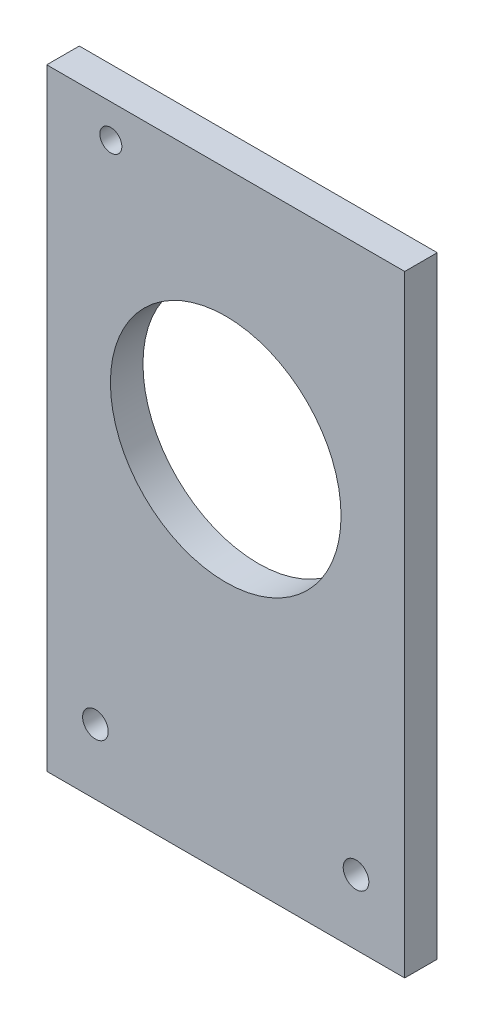
SolidWorks part; units mm, degrees
ref_plane "Front Plane" through (0, 0, 0) normal (0, 0, 1) x (1, 0, 0)
ref_plane "Top Plane" through (0, 0, 0) normal (0, 1, 0) x (1, 0, 0)
ref_plane "Right Plane" through (0, 0, 0) normal (1, 0, 0) x (0, 0, -1)
sketch "Sketch2" plane through (0, 0, 0) normal (0, 0, 1) x (1, 0, 0)
  line L0 (-55, 62.4) -> (55, 62.4) construction
  line L1 (-34.925, 0) -> (34.925, 0)
  line L2 (-34.925, 0) -> (-34.925, 71.9)
  line L3 (-34.925, 71.9) -> (34.925, 71.9) construction
  line L4 (34.925, 0) -> (34.925, 71.9)
  line L5 (0, 62.4) -> (0, 0) construction
  line L6 (0, 62.4) -> (0, 71.9) construction
  line L7 (-34.925, 25.4) -> (34.925, 25.4) construction
  line L10 (34.925, 104.4) -> (-34.925, 104.4) construction
  line L11 (34.925, 71.9) -> (34.925, 104.4)
  line L12 (34.925, 104.4) -> (-34.925, 104.4) construction
  line L13 (-34.925, 104.4) -> (-34.925, 71.9)
  line L14 (34.925, 104.4) -> (34.925, 119.4)
  line L15 (34.925, 119.4) -> (-34.925, 119.4)
  line L16 (-34.925, 104.4) -> (-34.925, 119.4)
  line L17 (-34.925, 25.4) -> (34.925, 25.4) construction
  circle A0 centre (-55, 62.4) radius 3 construction
  circle A1 centre (55, 62.4) radius 3 construction
  circle A2 centre (-55, 62.4) radius 15 construction
  circle A3 centre (55, 62.4) radius 15 construction
  circle A6 centre (0, 71.9) radius 22.5
  circle A7 centre (-55, 62.4) radius 15.6 construction
  point P6 (0, 0)
  dimension "D1" = 6
  dimension "D2" = 30
  dimension "D5" = 45
  dimension "D9" = 15
  dimension "D3" = 110
  dimension "D4" = 9.5
  dimension "D6" = 69.85
  dimension "D7" = 46.5
  dimension "D8" = 32.5
  dimension "D10" = 25.4
  dimension "D11" = 0.6
extrude "Boss-Extrude1" add sketch "Sketch2" along normal mid plane 6.35
sketch "Sketch3" plane through (0, 0, 3.175) normal (0, 0, 1) x (1, 0, 0)
  line L0 (34.925, 119.4) -> (-34.925, 119.4) construction
  line L1 (-34.925, 0) -> (-25.425, 0) construction
  line L2 (-34.925, 0) -> (-34.925, 12.7) construction
  line L3 (-34.925, 12.7) -> (-25.425, 12.7) construction
  line L4 (-25.425, 0) -> (-25.425, 12.7) construction
  line L5 (34.925, 0) -> (25.425, 0) construction
  line L6 (34.925, 0) -> (34.925, 12.7) construction
  line L7 (34.925, 12.7) -> (25.425, 12.7) construction
  line L8 (25.425, 0) -> (25.425, 12.7) construction
  line L9 (-34.925, 119.4) -> (-34.925, 0) construction
  circle A0 centre (-25.425, 12.7) radius 2.5
  circle A1 centre (25.425, 12.7) radius 2.5
  circle A2 centre (-22.425, 112.9) radius 2.15
  dimension "D1" = 12.7
  dimension "D2" = 5
  dimension "D4" = 4.3
  dimension "D5" = 6.5
  dimension "D3" = 9.5
  dimension "D6" = 12.5
extrude "Cut-Extrude1" cut sketch "Sketch3" against normal through all both and the other way through all
